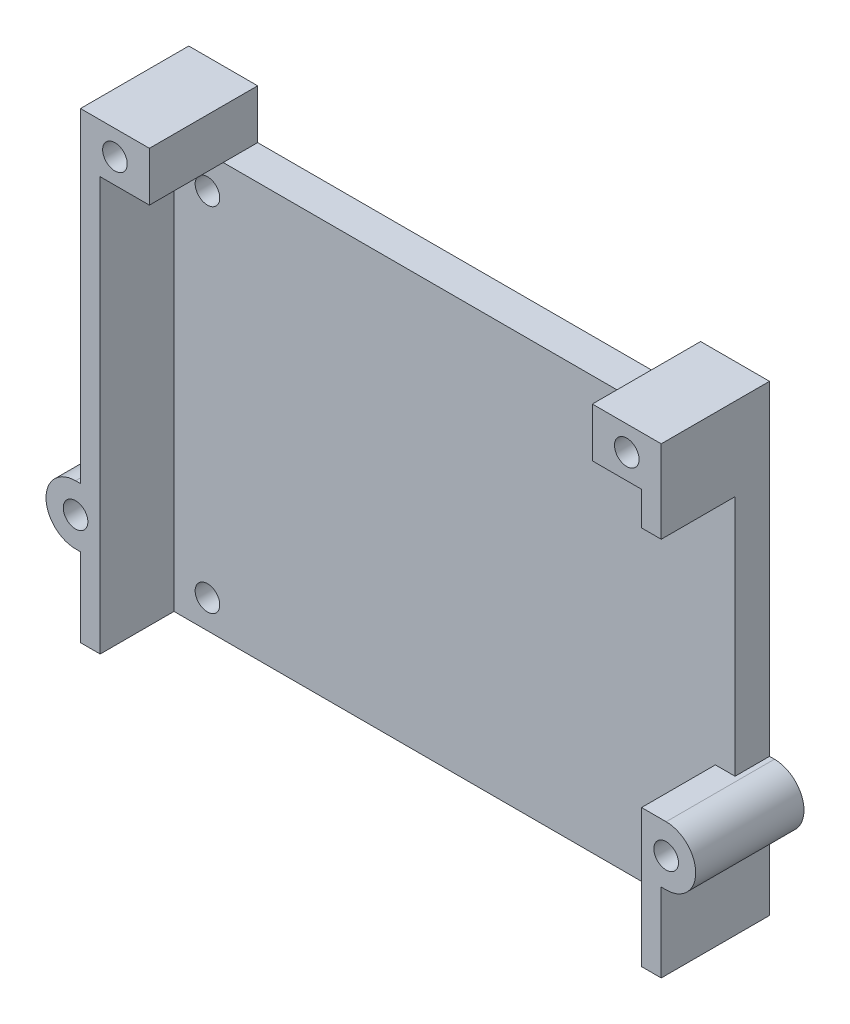
SolidWorks part; units mm, degrees
ref_plane "Front Plane" through (0, 0, 0) normal (0, 0, 1) x (1, 0, 0)
ref_plane "Top Plane" through (0, 0, 0) normal (0, 1, 0) x (1, 0, 0)
ref_plane "Right Plane" through (0, 0, 0) normal (1, 0, 0) x (0, 0, -1)
sketch "Sketch1" plane through (0, 0, 0) normal (0, 1, 0) x (1, 0, 0)
  line L0 (0, 0) -> (2, 0)
  line L1 (0, 0) -> (59, 0) construction
  line L2 (0, 0) -> (0, 11)
  line L3 (0, 11) -> (59, 11)
  line L4 (59, 0) -> (59, 11)
  line L5 (2, 0) -> (2, 7.5)
  line L6 (2, 7.5) -> (57, 7.5)
  line L7 (57, 7.5) -> (57, 0)
  line L8 (57, 0) -> (59, 0)
  dimension "D1" = 59
  dimension "D2" = 11
  dimension "D3" = 2
  dimension "D4" = 7.5
  dimension "D5" = 55
extrude "Boss-Extrude1" add sketch "Sketch1" along normal blind 42
sketch "Sketch2" plane through (59, 0, 0) normal (1, 0, 0) x (0, 0, -1)
  line L0 (0, 0) -> (0, 14) construction
  line L1 (0, 42) -> (0, 0) construction
  line L2 (0, 14) -> (7.5, 14)
  line L3 (7.5, 14) -> (7.5, 38.6)
  line L4 (7.5, 38.6) -> (0, 38.6)
  line L5 (0, 38.6) -> (0, 14)
  dimension "D1" = 14
  dimension "D2" = 7.5
  dimension "D3" = 24.6
extrude "Cut-Extrude1" cut sketch "Sketch2" against normal blind 10
sketch "Sketch3" plane through (0, 0, -11) normal (0, 0, -1) x (-1, 0, 0)
  line L0 (-59, 0) -> (-59, 14) construction
  line L1 (-59, 42) -> (-59, 0) construction
  line L2 (-59, 14) -> (-59, 8)
  line L3 (-59, 11) -> (-59.5, 11) construction
  line L4 (-59, 14) -> (-59.5, 14)
  line L5 (-59, 8) -> (-59.5, 8)
  line L6 (0, 0) -> (0, 14) construction
  line L7 (0, 42) -> (0, 0) construction
  line L8 (0, 14) -> (0.5, 14)
  line L9 (0, 14) -> (0, 8)
  line L10 (0, 8) -> (0.5, 8)
  line L11 (0, 11) -> (0.5, 11) construction
  arc A0 (-59.5, 14) -> (-59.5, 8) centre (-59.5, 11) ccw
  circle A1 centre (-59.5, 11) radius 1.25
  arc A2 (0.5, 14) -> (0.5, 8) centre (0.5, 11) cw
  circle A3 centre (0.5, 11) radius 1.25
  line M5 (0, 0) -> (0, 42)
  line M7 (-59, 42) -> (-59, 0)
  dimension "D4" = 3
  dimension "D5" = 2.5
  dimension "D11" = 3
  dimension "D12" = 2.5
  dimension "D1" = 14
  dimension "D2" = 6
  dimension "D3" = 0.5
  dimension "D6" = 14
  dimension "D7" = 0.5
  dimension "D8" = 6
extrude "Boss-Extrude2" add sketch "Sketch3" against normal blind 11 contours A1 L4 A0 L5 M7 | A3 L10 A2 L8 M5 region at (59.0695, 13.0728, -11) region at (-0.25, 13.9305, -11)
extrude "Cut-Extrude2" cut sketch "Sketch3<3>" against normal blind 11 contours L2 A1 | L9 A3 region at (58.6906, 11, -11) region at (0.3094, 11, -11)
sketch "Sketch3<3>" plane through (0, 0, -11) normal (0, 0, -1) x (-1, 0, 0) same geometry as "Sketch3"
sketch "Sketch4" plane through (0, 42, 0) normal (0, 1, 0) x (1, 0, 0)
  line L0 (59, 11) -> (0, 11) construction
  line L1 (0, 0) -> (7, 0)
  line L2 (0, 0) -> (0, 11)
  line L3 (0, 11) -> (7, 11)
  line L4 (7, 0) -> (7, 11)
  line L6 (59, 0) -> (52, 0)
  line L7 (59, 0) -> (59, 11)
  line L8 (59, 11) -> (52, 11)
  line L9 (52, 0) -> (52, 11)
  dimension "D1" = 7
  dimension "D2" = 7
extrude "Boss-Extrude3" add sketch "Sketch4" along normal blind 5
sketch "Sketch5" plane through (0, 0, -11) normal (0, 0, -1) x (-1, 0, 0)
  line L0 (-59, 47) -> (-52, 42) construction
  line L1 (0, 47) -> (-7, 42) construction
  circle A0 centre (-55.5, 44.5) radius 1.25
  circle A1 centre (-3.5, 44.5) radius 1.25
  dimension "D1" = 2.5
  dimension "D2" = 2.5
extrude "Cut-Extrude3" cut sketch "Sketch5" against normal through all
sketch "Sketch7" plane through (0, 0, -11) normal (0, 0, -1) x (-1, 0, 0)
  line L0 (-59, 0) -> (-59, 2.9) construction
  line L1 (-59, 8) -> (-59, 0) construction
  line L2 (-59, 2.9) -> (0, 2.9) construction
  line L3 (0, 8) -> (0, 0) construction
  line L4 (-53.6, 2.9) -> (-5.4, 2.9)
  line L5 (-53.6, 2.9) -> (-53.6, 38.7) construction
  line L6 (-53.6, 38.7) -> (-5.4, 38.7) construction
  circle A0 centre (-53.6, 2.9) radius 1.25
  circle A1 centre (-5.4, 2.9) radius 1.25
  circle A2 centre (-53.6, 38.7) radius 1.25
  circle A3 centre (-5.4, 38.7) radius 1.25
  point P11 (-29.5, 2.9)
  dimension "D3" = 2.5
  dimension "D4" = 2.5
  dimension "D6" = 2.5
  dimension "D8" = 2.5
  dimension "D1" = 2.9
  dimension "D2" = 48.2
  dimension "D5" = 35.8
  dimension "D7" = 48.2
extrude "Cut-Extrude4" cut sketch "Sketch7" against normal blind 10 contours A2 | A3 | A1 | A0 region at (5.4, 4.1146, -11) region at (54.8146, 2.9, -11) region at (53.6, 38.7, -11) region at (5.4, 38.7, -11)
